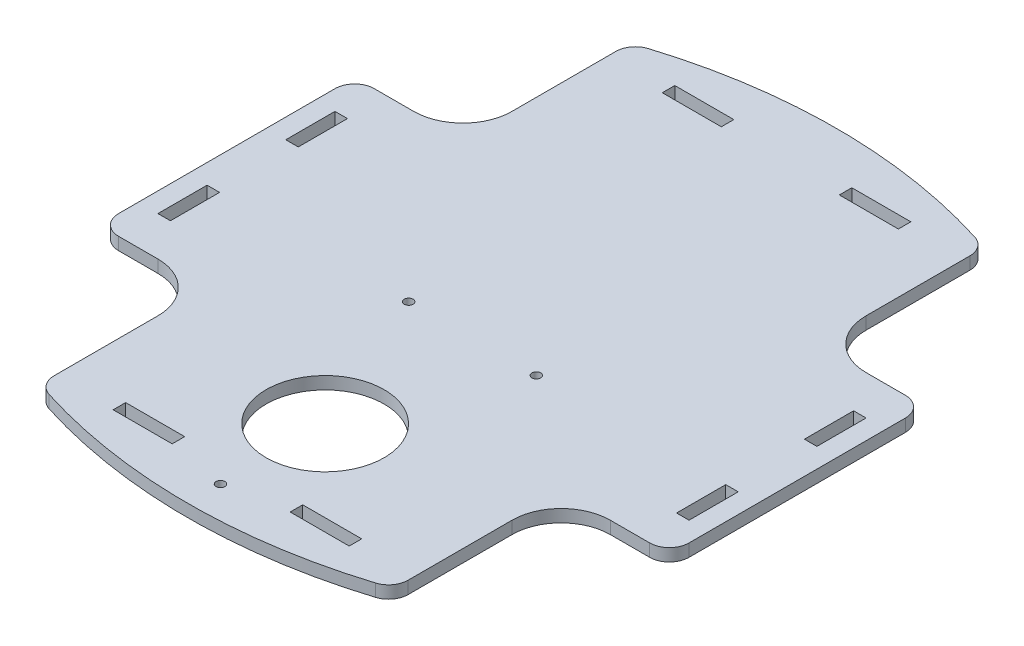
SolidWorks part; units mm, degrees
ref_plane "Plan de face" through (0, 0, 0) normal (0, 0, 1) x (1, 0, 0)
ref_plane "Plan de dessus" through (0, 0, 0) normal (0, 1, 0) x (1, 0, 0)
ref_plane "Plan de droite" through (0, 0, 0) normal (1, 0, 0) x (0, 0, -1)
sketch "Esquisse1" plane through (0, 0, 0) normal (0, 1, 0) x (1, 0, 0)
  line L0 (-145, 0) -> (0, 0) construction
  line L1 (-90, -150) -> (90, -150)
  line L2 (-90, -150) -> (-90, 150)
  line L3 (-90, 150) -> (90, 150)
  line L4 (90, -150) -> (90, 150)
  line L5 (-90, -150) -> (90, 150) construction
  line L6 (-90, 150) -> (90, -150) construction
  line L7 (-90, 65) -> (-145, 65)
  line L8 (-90, 65) -> (-90, -65)
  line L9 (-90, -65) -> (-145, -65)
  line L10 (-145, 65) -> (-145, -65)
  line L11 (0, 0) -> (0, -275) construction
  line L12 (90, -65) -> (145, -65)
  line L13 (145, 65) -> (145, -65)
  line L14 (90, 65) -> (145, 65)
  line L15 (90, 65) -> (90, -65)
  arc A0 (-90, 150) -> (90, 150) centre (0, -112.5) cw
  arc A1 (-90, -150) -> (90, -150) centre (0, 112.5) ccw
  point P0 (0, 0)
  point P19 (0, 165)
  point P20 (0, -165)
  dimension "D1" = 180
  dimension "D2" = 300
  dimension "D3" = 85
  dimension "D4" = 55
  dimension "D5" = 15
  dimension "D6" = 15
extrude "Boss.-Extru.1" add sketch "Esquisse1" along normal blind 6.35 contours L1 L4 L3 L2 | L7 L10 L9 L2 | L14 L4 L12 L13 | L1 A1 | A0 L3 region at (0, 0, 0) region at (0, 0, 156.0141) region at (-117.5, 0, 0) region at (117.5, 0, 0) region at (0, 0, -156.0141)
ref_plane "Plan1" through (0, 0, 150) normal (0, 0, -1) x (-1, 0, 0)
ref_plane "Plan3" through (0, 0, -150) normal (0, 0, -1) x (-1, 0, 0)
ref_plane "Wheel axis1" through (0, 0, 107.5) normal (0, 0, 1) x (1, 0, 0)
ref_plane "Wheel axis2" through (0, 0, -107.5) normal (0, 0, -1) x (-1, 0, 0)
fillet "Congé1" radius 25 4 edges at (90, 3.175, -65) (-90, 3.175, -65) (-90, 3.175, 65) (90, 3.175, 65)
fillet "Congé2" radius 10 8 edges at (-90, 3.175, -150) (-145, 3.175, -65) (-145, 3.175, 65) (-90, 3.175, 150) (90, 3.175, -150) (145, 3.175, -65) (145, 3.175, 65) (90, 3.175, 150)
sketch "Esquisse2" plane through (0, 6.35, 0) normal (0, 1, 0) x (1, 0, 0)
  line L0 (0, 0) -> (0, -95) construction
  circle A0 centre (0, -95) radius 30
  dimension "D1" = 60
  dimension "D2" = 95
extrude "Enlèv. mat.-Extru.1" cut sketch "Esquisse2" against normal up to next
sketch "Esquisse3" plane through (0, 6.35, 0) normal (0, 1, 0) x (1, 0, 0)
  circle A0 centre (-32.4307, -20.0639) radius 2.25 construction
  circle A1 centre (32.4307, -20.0639) radius 2.25 construction
  circle A2 centre (0, -148.1871) radius 2.25 construction
  circle A3 centre (-32.4307, -20.0639) radius 2.25
  circle A4 centre (32.4307, -20.0639) radius 2.25
  circle A5 centre (0, -148.1871) radius 2.25
extrude "Enlèv. mat.-Extru.2" cut sketch "Esquisse3" against normal up to next
sketch "Esquisse5" plane through (0, 6.35, 0) normal (0, 1, 0) x (1, 0, 0)
  line L0 (-30, 136.4072) -> (-30, 142.7572) construction
  line L1 (-30, 142.7572) -> (-60, 142.7572) construction
  line L2 (-60, 142.7572) -> (-60, 136.4072) construction
  line L3 (-60, 136.4072) -> (-30, 136.4072) construction
  line L4 (60, 136.4072) -> (60, 142.7572) construction
  line L5 (60, 142.7572) -> (30, 142.7572) construction
  line L6 (30, 142.7572) -> (30, 136.4072) construction
  line L7 (30, 136.4072) -> (60, 136.4072) construction
  line L8 (-30, -142.7572) -> (-30, -136.4072) construction
  line L9 (-30, -136.4072) -> (-60, -136.4072) construction
  line L10 (-60, -136.4072) -> (-60, -142.7572) construction
  line L11 (-60, -142.7572) -> (-30, -142.7572) construction
  line L12 (60, -142.7572) -> (60, -136.4072) construction
  line L13 (60, -136.4072) -> (30, -136.4072) construction
  line L14 (30, -136.4072) -> (30, -142.7572) construction
  line L15 (30, -142.7572) -> (60, -142.7572) construction
  line L16 (135, -20) -> (128.65, -20) construction
  line L17 (128.65, -20) -> (128.65, -45) construction
  line L18 (128.65, -45) -> (135, -45) construction
  line L19 (135, -45) -> (135, -20) construction
  line L20 (135, 45) -> (128.65, 45) construction
  line L21 (128.65, 45) -> (128.65, 20) construction
  line L22 (128.65, 20) -> (135, 20) construction
  line L23 (135, 20) -> (135, 45) construction
  line L24 (-128.65, 45) -> (-135, 45) construction
  line L25 (-135, 45) -> (-135, 20) construction
  line L26 (-135, 20) -> (-128.65, 20) construction
  line L27 (-128.65, 20) -> (-128.65, 45) construction
  line L28 (-128.65, -20) -> (-135, -20) construction
  line L29 (-135, -20) -> (-135, -45) construction
  line L30 (-135, -45) -> (-128.65, -45) construction
  line L31 (-128.65, -45) -> (-128.65, -20) construction
  line L32 (-30, 136.4072) -> (-30, 142.7572)
  line L33 (-30, 142.7572) -> (-60, 142.7572)
  line L34 (-60, 142.7572) -> (-60, 136.4072)
  line L35 (-60, 136.4072) -> (-30, 136.4072)
  line L36 (60, 136.4072) -> (60, 142.7572)
  line L37 (60, 142.7572) -> (30, 142.7572)
  line L38 (30, 142.7572) -> (30, 136.4072)
  line L39 (30, 136.4072) -> (60, 136.4072)
  line L40 (-30, -142.7572) -> (-30, -136.4072)
  line L41 (-30, -136.4072) -> (-60, -136.4072)
  line L42 (-60, -136.4072) -> (-60, -142.7572)
  line L43 (-60, -142.7572) -> (-30, -142.7572)
  line L44 (60, -142.7572) -> (60, -136.4072)
  line L45 (60, -136.4072) -> (30, -136.4072)
  line L46 (30, -136.4072) -> (30, -142.7572)
  line L47 (30, -142.7572) -> (60, -142.7572)
  line L48 (135, -20) -> (128.65, -20)
  line L49 (128.65, -20) -> (128.65, -45)
  line L50 (128.65, -45) -> (135, -45)
  line L51 (135, -45) -> (135, -20)
  line L52 (135, 45) -> (128.65, 45)
  line L53 (128.65, 45) -> (128.65, 20)
  line L54 (128.65, 20) -> (135, 20)
  line L55 (135, 20) -> (135, 45)
  line L56 (-128.65, 45) -> (-135, 45)
  line L57 (-135, 45) -> (-135, 20)
  line L58 (-135, 20) -> (-128.65, 20)
  line L59 (-128.65, 20) -> (-128.65, 45)
  line L60 (-128.65, -20) -> (-135, -20)
  line L61 (-135, -20) -> (-135, -45)
  line L62 (-135, -45) -> (-128.65, -45)
  line L63 (-128.65, -45) -> (-128.65, -20)
extrude "Enlèv. mat.-Extru.3" cut sketch "Esquisse5" against normal up to next
